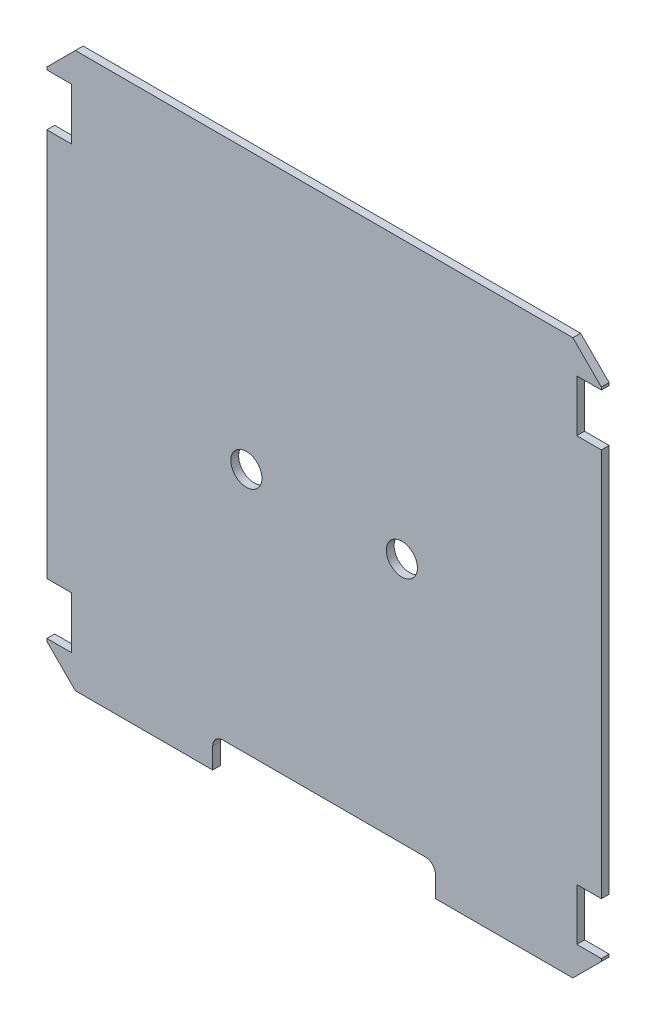
SolidWorks part; units mm, degrees
material "1060 Alloy"
ref_plane "Front Plane" through (0, 0, 0) normal (0, 0, 1) x (1, 0, 0)
ref_plane "Top Plane" through (0, 0, 0) normal (0, 1, 0) x (1, 0, 0)
ref_plane "Right Plane" through (0, 0, 0) normal (1, 0, 0) x (0, 0, -1)
sketch "Sketch1" plane through (0, 0, 0) normal (0, 0, 1) x (1, 0, 0)
  line L0 (-100, -100) -> (100, -100) construction
  line L1 (-100, -100) -> (-100, 100) construction
  line L2 (100, -100) -> (100, 100) construction
  line L3 (-100, 100) -> (100, 100) construction
  line L4 (-100, -100) -> (100, 100) construction
  line L5 (100, -100) -> (-100, 100) construction
  line L6 (-107, 0) -> (107, 0) construction
  line L7 (-107, -107) -> (107, -107)
  line L8 (-107, -107) -> (-107, 107)
  line L9 (-107, 107) -> (107, 107)
  line L10 (107, -107) -> (107, 107)
  line L11 (-107, -107) -> (107, 107) construction
  line L12 (-107, 107) -> (107, -107) construction
  circle A0 centre (-104.5, 104.5) radius 1.6 construction
  circle A1 centre (104.5, 104.5) radius 1.6 construction
  circle A2 centre (0, -104.5) radius 1.6
  circle A3 centre (104.5, -104.5) radius 1.6 construction
  circle A4 centre (-104.5, -104.5) radius 1.6 construction
  point P0 (0, 0)
  point P1 (0, 0)
  dimension "D4" = 3.2
  dimension "D1" = 209
  dimension "D2" = 200
  dimension "D3" = 214
  dimension "D5" = 209
extrude "Boss-Extrude1" add sketch "Sketch1" along normal blind 3
sketch "Sketch2" plane through (0, 0, 3) normal (0, 0, 1) x (1, 0, 0)
  line L0 (-107, -107) -> (107, -107) construction
  line L1 (-43, -107) -> (43, -107)
  line L2 (-43, -107) -> (-43, -95)
  line L3 (-43, -95) -> (43, -95)
  line L4 (43, -107) -> (43, -95)
  line L5 (-107, 107) -> (-107, -107) construction
  line L6 (-107, -95) -> (-97.5051, -95)
  line L7 (-107, -95) -> (-107, -75)
  line L8 (-107, -75) -> (-97.5051, -75)
  line L9 (-97.5051, -95) -> (-97.5051, -75)
  line L10 (107, -107) -> (107, 107) construction
  line L11 (-107, 75) -> (-97.5051, 75)
  line L12 (-107, 75) -> (-107, 95)
  line L13 (-107, 95) -> (-97.5051, 95)
  line L14 (-97.5051, 75) -> (-97.5051, 95)
  line L15 (107, 75) -> (97.5051, 75)
  line L16 (107, 75) -> (107, 95)
  line L17 (107, 95) -> (97.5051, 95)
  line L18 (97.5051, 75) -> (97.5051, 95)
  line L19 (-97.5051, -75) -> (97.5051, 75) construction
  line L20 (107, -95) -> (97.5051, -95)
  line L21 (107, -95) -> (107, -75)
  line L22 (107, -75) -> (97.5051, -75)
  line L23 (97.5051, -95) -> (97.5051, -75)
  line L24 (-97.5051, 75) -> (97.5051, -75) construction
  line L25 (-30, 0) -> (30, 0) construction
  circle A0 centre (30, 0) radius 6
  circle A1 centre (-30, 0) radius 6
  dimension "D7" = 12
  dimension "D1" = 12
  dimension "D2" = 43
  dimension "D3" = 86
  dimension "D4" = 20
  dimension "D5" = 12
  dimension "D6" = 30
extrude "Cut-Extrude1" cut sketch "Sketch2" against normal through all
fillet "Fillet1" radius 4 2 edges at (43, -95, 1.5) (-43, -95, 1.5)
chamfer "Chamfer1" distance 11 angle 45 4 edges at (107, 107, 1.5) (-107, 107, 1.5) (-107, -107, 1.5) (107, -107, 1.5)
